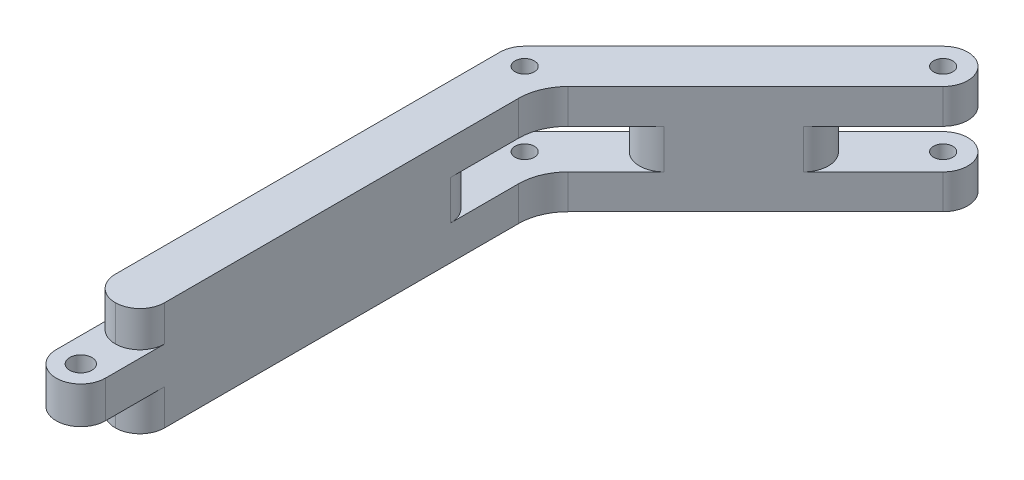
SolidWorks part; units mm, degrees
ref_plane "Plan de face" through (0, 0, 0) normal (0, 0, 1) x (1, 0, 0)
ref_plane "Plan de dessus" through (0, 0, 0) normal (0, 1, 0) x (1, 0, 0)
ref_plane "Plan de droite" through (0, 0, 0) normal (1, 0, 0) x (0, 0, -1)
sketch "Esquisse2" plane through (0, 0, 0) normal (0, 1, 0) x (1, 0, 0)
  line L0 (0, 0) -> (0, 90) construction
  line L1 (-5, 0) -> (-5, 90)
  line L2 (5, 0) -> (5, 90)
  line L3 (0, 90) -> (42.4264, 132.4264) construction
  line L4 (-3.5355, 93.5355) -> (38.8909, 135.9619)
  line L5 (3.5355, 86.4645) -> (45.9619, 128.8909)
  arc A0 (-5, 0) -> (5, 0) centre (0, 0) ccw
  arc A1 (5, 90) -> (-5, 90) centre (0, 90) ccw
  arc A2 (-3.5355, 93.5355) -> (3.5355, 86.4645) centre (0, 90) ccw
  arc A3 (45.9619, 128.8909) -> (38.8909, 135.9619) centre (42.4264, 132.4264) ccw
  circle A4 centre (42.4264, 132.4264) radius 1.95
  circle A5 centre (0, 90) radius 1.95
  point P3 (0, 45)
  point P8 (21.2132, 111.2132)
  dimension "D2" = 3.9
  dimension "D3" = 3.9
  dimension "D4" = 3.05
  dimension "D5" = 60
  dimension "D1" = 135
  dimension "D6" = 90
extrude "Boss.-Extru.1" add sketch "Esquisse2" along normal blind 7 contours A2 L1 A0 L2 L5 | L5 A3 L4 A1 L2 A4 | A1 A2 L5 L2 A5 region at (-0.0028, 0, -41.0449) region at (-4.4887, 0, -91.8593) region at (23.6328, 0, -113.6389)
fillet "Congé1" radius 10 1 edges at (5, 3.5, -87.9289)
sketch "Esquisse3" plane through (0, 7, 0) normal (0, 1, 0) x (1, 0, 0)
  line L0 (0, 0) -> (0, 70) construction
  line L1 (-5, 0) -> (-5, 70)
  line L2 (5, 0) -> (5, 70)
  line L3 (28.2843, 118.2843) -> (14.1421, 104.1421) construction
  line L4 (31.8198, 114.7487) -> (17.6777, 100.6066)
  line L5 (24.7487, 121.8198) -> (10.6066, 107.6777)
  line L6 (5, 0) -> (5, 83.7868) construction
  line L7 (-3.5355, 93.5355) -> (38.8909, 135.9619) construction
  line L9 (7.9289, 90.8579) -> (45.9619, 128.8909) construction
  arc A0 (-5, 0) -> (5, 0) centre (0, 0) ccw
  arc A1 (5, 70) -> (-5, 70) centre (0, 70) ccw
  arc A2 (31.8198, 114.7487) -> (24.7487, 121.8198) centre (28.2843, 118.2843) ccw
  arc A3 (10.6066, 107.6777) -> (17.6777, 100.6066) centre (14.1421, 104.1421) ccw
  circle A4 centre (0, 90) radius 1.95 construction
  point P3 (0, 35)
  point P8 (21.2132, 111.2132)
  dimension "D1" = 20
  dimension "D2" = 20
  dimension "D3" = 70
extrude "Boss.-Extru.2" add sketch "Esquisse3" along normal blind 8
sketch "Esquisse4" plane through (0, 15, 0) normal (0, 1, 0) x (1, 0, 0)
  line L0 (5, 0) -> (5, 70) construction
  line L1 (-5, 70) -> (-5, 0) construction
  line L2 (7.9289, 90.8579) -> (17.6777, 100.6066) construction
  line L3 (10.6066, 107.6777) -> (-3.5355, 93.5355) construction
  line L4 (-5, 90) -> (-5, 70) construction
  line L5 (5, 70) -> (5, 83.7868) construction
  line L6 (24.7487, 121.8198) -> (10.6066, 107.6777) construction
  line L7 (17.6777, 100.6066) -> (31.8198, 114.7487) construction
  line L8 (38.8909, 135.9619) -> (24.7487, 121.8198) construction
  line L9 (31.8198, 114.7487) -> (45.9619, 128.8909) construction
  line L10 (5, 0) -> (5, 70)
  line L11 (-5, 70) -> (-5, 0)
  line L12 (7.9289, 90.8579) -> (17.6777, 100.6066)
  line L13 (10.6066, 107.6777) -> (-3.5355, 93.5355)
  line L14 (-5, 90) -> (-5, 70)
  line L15 (5, 70) -> (5, 83.7868)
  line L16 (24.7487, 121.8198) -> (10.6066, 107.6777)
  line L17 (17.6777, 100.6066) -> (31.8198, 114.7487)
  line L18 (38.8909, 135.9619) -> (24.7487, 121.8198)
  line L19 (31.8198, 114.7487) -> (45.9619, 128.8909)
  arc A0 (-5, 0) -> (5, 0) centre (0, 0) ccw construction
  arc A1 (5, 70) -> (-5, 70) centre (0, 70) ccw construction
  arc A2 (10.6066, 107.6777) -> (17.6777, 100.6066) centre (14.1421, 104.1421) ccw construction
  arc A3 (-3.5355, 93.5355) -> (-5, 90) centre (0, 90) ccw construction
  arc A4 (5, 70) -> (-5, 70) centre (0, 70) ccw construction
  arc A5 (7.9289, 90.8579) -> (5, 83.7868) centre (15, 83.7868) ccw construction
  arc A6 (31.8198, 114.7487) -> (24.7487, 121.8198) centre (28.2843, 118.2843) ccw construction
  arc A7 (10.6066, 107.6777) -> (17.6777, 100.6066) centre (14.1421, 104.1421) ccw construction
  arc A8 (31.8198, 114.7487) -> (24.7487, 121.8198) centre (28.2843, 118.2843) ccw construction
  arc A9 (45.9619, 128.8909) -> (38.8909, 135.9619) centre (42.4264, 132.4264) ccw construction
  arc A10 (-5, 0) -> (5, 0) centre (0, 0) ccw
  arc A11 (5, 70) -> (-5, 70) centre (0, 70) ccw
  arc A12 (10.6066, 107.6777) -> (17.6777, 100.6066) centre (14.1421, 104.1421) ccw
  arc A13 (-3.5355, 93.5355) -> (-5, 90) centre (0, 90) ccw
  arc A14 (5, 70) -> (-5, 70) centre (0, 70) ccw
  arc A15 (7.9289, 90.8579) -> (5, 83.7868) centre (15, 83.7868) ccw
  arc A16 (31.8198, 114.7487) -> (24.7487, 121.8198) centre (28.2843, 118.2843) ccw
  arc A17 (10.6066, 107.6777) -> (17.6777, 100.6066) centre (14.1421, 104.1421) ccw
  arc A18 (31.8198, 114.7487) -> (24.7487, 121.8198) centre (28.2843, 118.2843) ccw
  arc A19 (45.9619, 128.8909) -> (38.8909, 135.9619) centre (42.4264, 132.4264) ccw
  circle A20 centre (0, 90) radius 1.95 construction
  circle A21 centre (42.4264, 132.4264) radius 1.95 construction
  circle A22 centre (0, 90) radius 1.95
  circle A23 centre (42.4264, 132.4264) radius 1.95
  arc M1 (-5, 0) -> (5, 0) centre (0, 0) ccw
  line M2 (5, 0) -> (5, 70)
  arc M3 (5, 70) -> (-5, 70) centre (0, 70) ccw
  line M4 (-5, 70) -> (-5, 0)
extrude "Boss.-Extru.3" add sketch "Esquisse4" along normal blind 7 contours L19 A19 L18 A16 A23 | L17 A16 L16 A12 | A15 L12 A12 L13 A13 L14 L15 A22 M3 | M4 M1 M2 M3 region at (0, 15, -35) region at (2.7911, 15, -88.8439) region at (21.2132, 15, -111.2132) region at (37.8594, 15, -127.8594)
sketch "Esquisse5" plane through (0, 22, 0) normal (0, 1, 0) x (1, 0, 0)
  line L0 (-5, 0) -> (-5, 7)
  line L1 (-5, 90) -> (-5, 0) construction
  line L2 (-5, 7) -> (5, 7)
  line L3 (5, 0) -> (5, 83.7868) construction
  line L4 (5, 7) -> (5, 0)
  arc A0 (-5, 0) -> (5, 0) centre (0, 0) ccw
  dimension "D1" = 7
extrude "Enlèv. mat.-Extru.1" cut sketch "Esquisse5" against normal blind 7.25
ref_plane "Plan1" through (0, 11, 0) normal (0, -1, 0) x (-1, 0, 0)
mirror "Symétrie1" about plane through (0, 11, 0) normal (0, -1, 0) of "Enlèv. mat.-Extru.1"
sketch "Esquisse6" plane through (0, 14.75, 0) normal (0, 1, 0) x (1, 0, 0)
  circle A0 centre (0, 0) radius 2.25
  dimension "D1" = 4.5
extrude "Enlèv. mat.-Extru.2" cut sketch "Esquisse6" against normal through all contours A0
fillet "Congé2" radius 5 4 edges at (5, 18.375, -7) (-5, 18.375, -7) (5, 3.625, -7) (-5, 3.625, -7)
